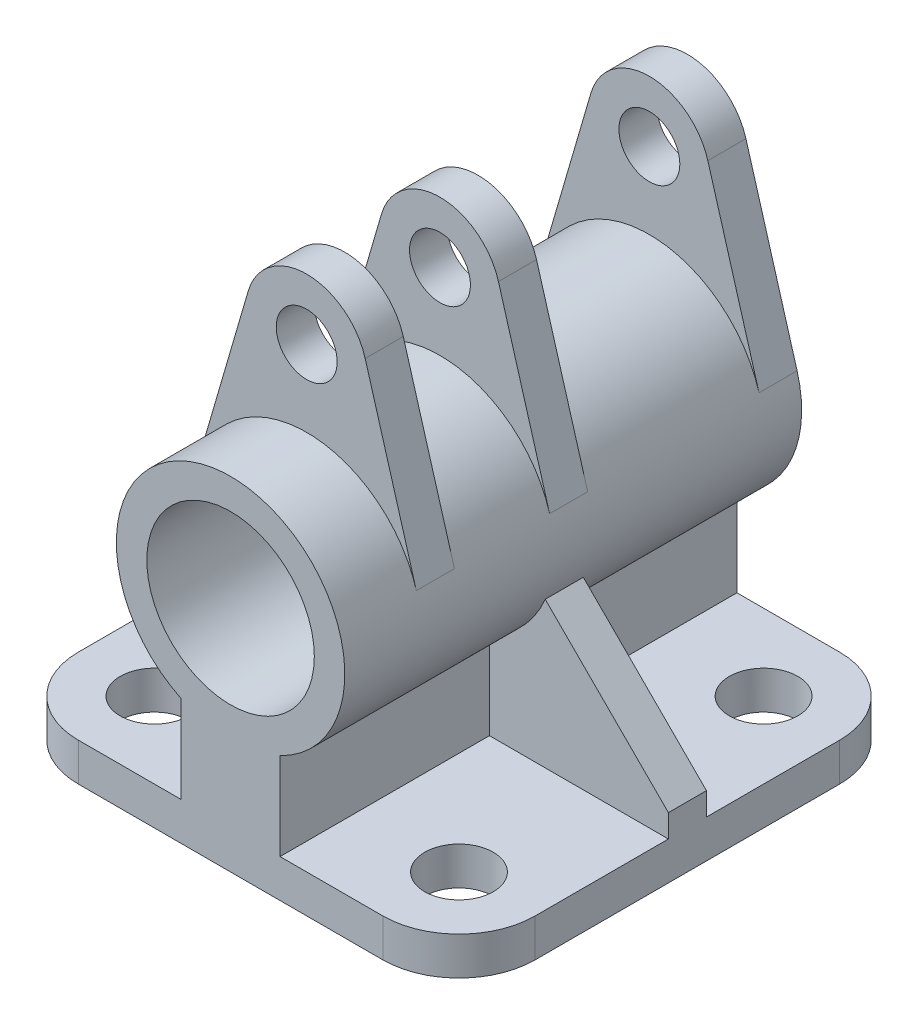
SolidWorks part; units mm, degrees
ref_plane "Спереди" through (0, 0, 0) normal (0, 0, 1) x (1, 0, 0)
ref_plane "Сверху" through (0, 0, 0) normal (0, 1, 0) x (1, 0, 0)
ref_plane "Справа" through (0, 0, 0) normal (1, 0, 0) x (0, 0, -1)
sketch "Эскиз1" plane through (0, 0, 0) normal (0, 0, 1) x (1, 0, 0)
  line L0 (0, 52.1447) -> (0, -44.8014) construction
  line L1 (6.5, -13.5185) -> (6.5, -25)
  line L2 (6.5, -25) -> (30, -25)
  line L3 (30, -25) -> (30, -22)
  line L4 (30, -22) -> (13.8234, -5.8234)
  line L5 (30, -25) -> (30, -30)
  line L6 (30, -30) -> (-30, -30)
  line L7 (7.68, 27.24) -> (14.4, 4.2)
  line L8 (-7.68, 27.24) -> (-14.4, 4.2)
  line L9 (-30, -25) -> (-30, -30)
  line L10 (-30, -22) -> (-13.8234, -5.8234)
  line L11 (-30, -25) -> (-30, -22)
  line L12 (-6.5, -25) -> (-30, -25)
  line L13 (-6.5, -13.5185) -> (-6.5, -25)
  circle A0 centre (0, 0) radius 11
  circle A1 centre (0, 0) radius 15
  circle A2 centre (0, 25) radius 4
  arc A3 (7.68, 27.24) -> (-7.68, 27.24) centre (0, 25) ccw
  point P21 (0, -30)
  dimension "D1" = 30
  dimension "D2" = 22
  dimension "D9" = 8
  dimension "D11" = 16
  dimension "D3" = 8
  dimension "D4" = 30
  dimension "D5" = 30
  dimension "D6" = 6.5
  dimension "D7" = 5
  dimension "D8" = 45
  dimension "D10" = 55
extrude "Бобышка-Вытянуть5" add sketch "Эскиз1" along normal mid plane 60 contours A1 L0 A0 | L0 A1 A0 | A1 L0 L6 L5 L2 L1 | L0 A1 L13 L12 L9 L6 region at (14.5172, 2.0739, 0) region at (-8.7988, 11.7317, 0) region at (-11.3532, -25.0787, 0) region at (11.3532, -25.0787, 0)
extrude "Бобышка-Вытянуть7" add sketch "Эскиз1<6>" along normal mid plane 5 contours A3 L0 A2 A1 L7 | L0 A3 L8 A1 A2 | A1 L1 L2 L3 L4 | A1 L10 L11 L12 L13 region at (5.7093, 20.665, 0) region at (-5.7093, 20.665, 0) region at (-16.4394, -18.1684, 0) region at (16.4394, -18.1684, 0)
sketch "Эскиз1<6>" plane through (0, 0, 0) normal (0, 0, 1) x (1, 0, 0) same geometry as "Эскиз1"
extrude "Бобышка-Вытянуть8" add sketch "Эскиз1<8>" along normal blind 5 from offset 15 contours A3 L0 A2 A1 L7 | L0 A3 L8 A1 A2 region at (5.7093, 20.665, 0) region at (-5.7093, 20.665, 0)
sketch "Эскиз1<8>" plane through (0, 0, 0) normal (0, 0, 1) x (1, 0, 0) same geometry as "Эскиз1"
extrude "Бобышка-Вытянуть9" add sketch "Эскиз1<9>" along normal blind 5 from vertex contours L0 A3 L8 A1 A2 | A3 L0 A2 A1 L7 region at (5.7093, 20.665, 0) region at (-5.7093, 20.665, 0) starting at point (30, -25, -30)
sketch "Эскиз1<9>" plane through (0, 0, 0) normal (0, 0, 1) x (1, 0, 0) same geometry as "Эскиз1"
sketch "Эскиз3" plane through (0, -30, 0) normal (0, -1, 0) x (1, 0, 0)
  line L0 (0, 35.9357) -> (0, -37.1095) construction
  line L1 (38.6145, 0) -> (-40.9869, 0) construction
  circle A0 centre (20, -20) radius 4.5
  circle A1 centre (20, 20) radius 4.5
  circle A2 centre (-20, -20) radius 4.5
  circle A3 centre (-20, 20) radius 4.5
  dimension "D1" = 20
  dimension "D3" = 9
  dimension "D2" = 20
extrude "Вырез-Вытянуть1" cut sketch "Эскиз3" against normal through all
fillet "Скругление1" radius 10 4 edges at (30, -27.5, -30) (30, -27.5, 30) (-30, -27.5, 30) (-30, -27.5, -30)
